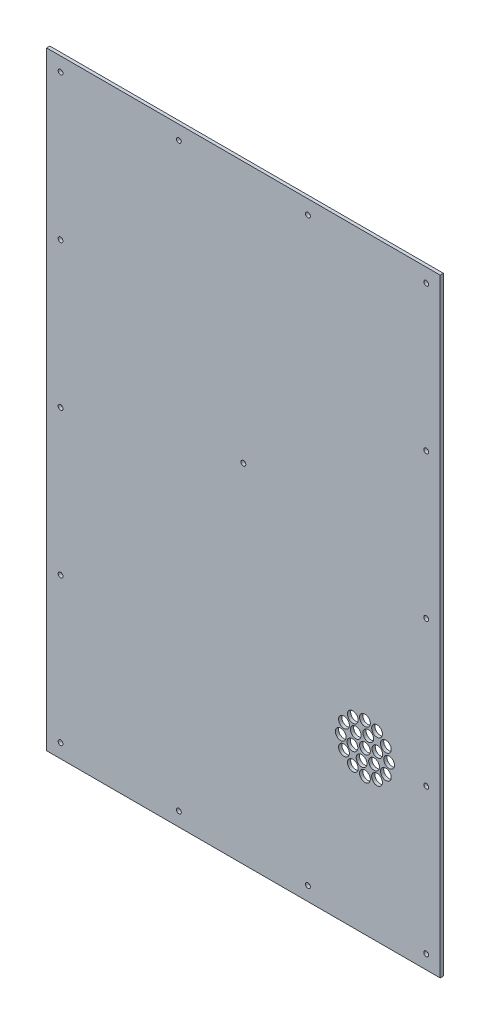
SolidWorks part; units mm, degrees
ref_plane "Спереди" through (0, 0, 0) normal (0, 0, 1) x (1, 0, 0)
ref_plane "Сверху" through (0, 0, 0) normal (0, 1, 0) x (1, 0, 0)
ref_plane "Справа" through (0, 0, 0) normal (1, 0, 0) x (0, 0, -1)
sketch "Эскиз1" plane through (0, 0, 0) normal (0, 0, 1) x (1, 0, 0)
  line L0 (0, 0) -> (366, 0)
  line L1 (0, 0) -> (0, 566)
  line L2 (366, 0) -> (366, 566)
  line L3 (0, 566) -> (366, 566)
  dimension "D1" = 566
  dimension "D2" = 366
extrude "Бобышка-Вытянуть1" add sketch "Эскиз1" along normal blind 3
sketch "Эскиз2" plane through (0, 0, 3) normal (0, 0, 1) x (1, 0, 0)
  line L0 (3, 563) -> (363, 563) construction
  line L1 (3, 563) -> (3, 3) construction
  line L2 (363, 563) -> (363, 3) construction
  line L3 (3, 3) -> (363, 3) construction
  line L4 (0, 566) -> (0, 0) construction
  line L5 (0, 0) -> (366, 0) construction
  dimension "D1" = 560
  dimension "D2" = 360
  dimension "D3" = 3
  dimension "D4" = 3
sketch "Эскиз5" plane through (0, 0, 0) normal (0, 0, -1) x (-1, 0, 0)
  line L0 (-353, 553) -> (-13, 553) construction
  line L1 (-353, 553) -> (-353, 13) construction
  line L2 (-13, 553) -> (-13, 13) construction
  line L3 (-353, 13) -> (-13, 13) construction
  line L4 (-366, 566) -> (0, 566) construction
  line L5 (-366, 0) -> (-366, 566) construction
  line L6 (0, 566) -> (0, 0) construction
  line L7 (0, 0) -> (-366, 0) construction
  line L8 (-366, 23) -> (-343, 23) construction
  line L9 (-366, 23) -> (-366, 0) construction
  line L10 (-343, 23) -> (-343, 0) construction
  line L11 (-366, 0) -> (-343, 0) construction
  line L12 (0, 0) -> (0, 23) construction
  line L13 (0, 0) -> (-23, 0) construction
  line L14 (0, 23) -> (-23, 23) construction
  line L15 (-23, 0) -> (-23, 23) construction
  line L16 (-366, 566) -> (-343, 566) construction
  line L17 (-366, 566) -> (-366, 543) construction
  line L18 (-343, 566) -> (-343, 543) construction
  line L19 (-366, 543) -> (-343, 543) construction
  line L20 (0, 566) -> (0, 543) construction
  line L21 (0, 566) -> (-23, 566) construction
  line L22 (0, 543) -> (-23, 543) construction
  line L23 (-23, 566) -> (-23, 543) construction
  line L24 (-13, 283) -> (-353, 283) construction
  line L25 (-183, 553) -> (-183, 13) construction
  line L26 (0, 0) -> (-366, 0) construction
  circle A0 centre (-353, 553) radius 2.25
  circle A1 centre (-13, 553) radius 2.25
  circle A3 centre (-243, 553) radius 2.25
  circle A4 centre (-123, 553) radius 2.25
  circle A5 centre (-353, 418) radius 2.25
  circle A6 centre (-353, 283) radius 2.25
  circle A7 centre (-353, 148) radius 2.25
  circle A8 centre (-353, 13) radius 2.25
  circle A9 centre (-123, 13) radius 2.25
  circle A10 centre (-243, 13) radius 2.25
  circle A11 centre (-13, 418) radius 2.25
  circle A12 centre (-13, 283) radius 2.25
  circle A13 centre (-13, 148) radius 2.25
  circle A14 centre (-13, 13) radius 2.25
  dimension "D13" = 4.5
  dimension "D14" = 4.5
  dimension "D15" = 110
  dimension "D17" = 4.5
  dimension "D18" = 4.5
  dimension "D19" = 110
  dimension "D22" = 135
  dimension "D23" = 135
  dimension "D24" = 110
  dimension "D25" = 5
  dimension "D26" = 135
  dimension "D27" = 110
  dimension "D28" = 120
  dimension "D29" = 4.5
  dimension "D30" = 4.5
  dimension "D1" = 13
  dimension "D2" = 13
  dimension "D3" = 13
  dimension "D4" = 13
  dimension "D5" = 23
  dimension "D6" = 23
  dimension "D7" = 23
  dimension "D8" = 23
  dimension "D9" = 23
  dimension "D10" = 23
  dimension "D11" = 23
  dimension "D12" = 23
  dimension "D21" = 5
extrude "Вырез-Вытянуть2" cut sketch "Эскиз5" against normal through all
sketch "Sketch1" plane through (0, 0, 3) normal (0, 0, 1) x (1, 0, 0)
  line L1 (343, 333) -> (23, 333) construction
  line L2 (183, 333) -> (183, 323) construction
  circle A0 centre (183, 323) radius 2.25
  dimension "D1" = 4.5
  dimension "D2" = 10
extrude "Cut-Extrude1" cut sketch "Sketch1" against normal through all
sketch "Эскиз6" plane through (0, 0, 0) normal (0, 0, -1) x (-1, 0, 0)
  line L0 (-296, 150) -> (-296, 122.5) construction
  line L3 (-296, 150) -> (-308, 150) construction
  line L5 (-296, 150) -> (-304.4853, 141.5147) construction
  arc A0 (-304, 123.6894) -> (-270.3826, 140) centre (-296, 150) ccw construction
  arc A1 (-304, 123.6894) -> (-270.3826, 140) centre (-296, 150) ccw construction
  circle A2 centre (-296, 150) radius 27.5 construction
  circle A3 centre (-296, 150) radius 22.5 construction
  circle A4 centre (-296, 150) radius 12 construction
  circle A5 centre (-296, 127.5) radius 5
  circle A6 centre (-307.25, 130.5144) radius 5
  circle A7 centre (-315.4856, 138.75) radius 5
  circle A8 centre (-318.5, 150) radius 5
  circle A9 centre (-315.4856, 161.25) radius 5
  circle A10 centre (-307.25, 169.4856) radius 5
  circle A11 centre (-296, 172.5) radius 5
  circle A12 centre (-284.75, 169.4856) radius 5
  circle A13 centre (-276.5144, 161.25) radius 5
  circle A14 centre (-273.5, 150) radius 5
  circle A15 centre (-292.8942, 138.4089) radius 5
  circle A16 centre (-304.4853, 141.5147) radius 5
  circle A17 centre (-307.5911, 153.1058) radius 5
  circle A18 centre (-299.1058, 161.5911) radius 5
  circle A19 centre (-287.5147, 158.4853) radius 5
  circle A20 centre (-296, 150) radius 5
  circle A21 centre (-276.5144, 138.75) radius 5
  circle A22 centre (-284.4089, 146.8942) radius 5
  circle A24 centre (-284.75, 130.5144) radius 5
  point P30 (-296, 150)
  point P40 (-296, 150)
  point P54 (-296, 150)
  dimension "D1" = 10
  dimension "D2" = 45
  dimension "D5" = 6
  dimension "D6" = 45
  dimension "D7" = 24
  dimension "D10" = 10
  dimension "D4" = 10
  dimension "D3" = 12
extrude "Вырез-Вытянуть3" cut sketch "Эскиз6" against normal through all
